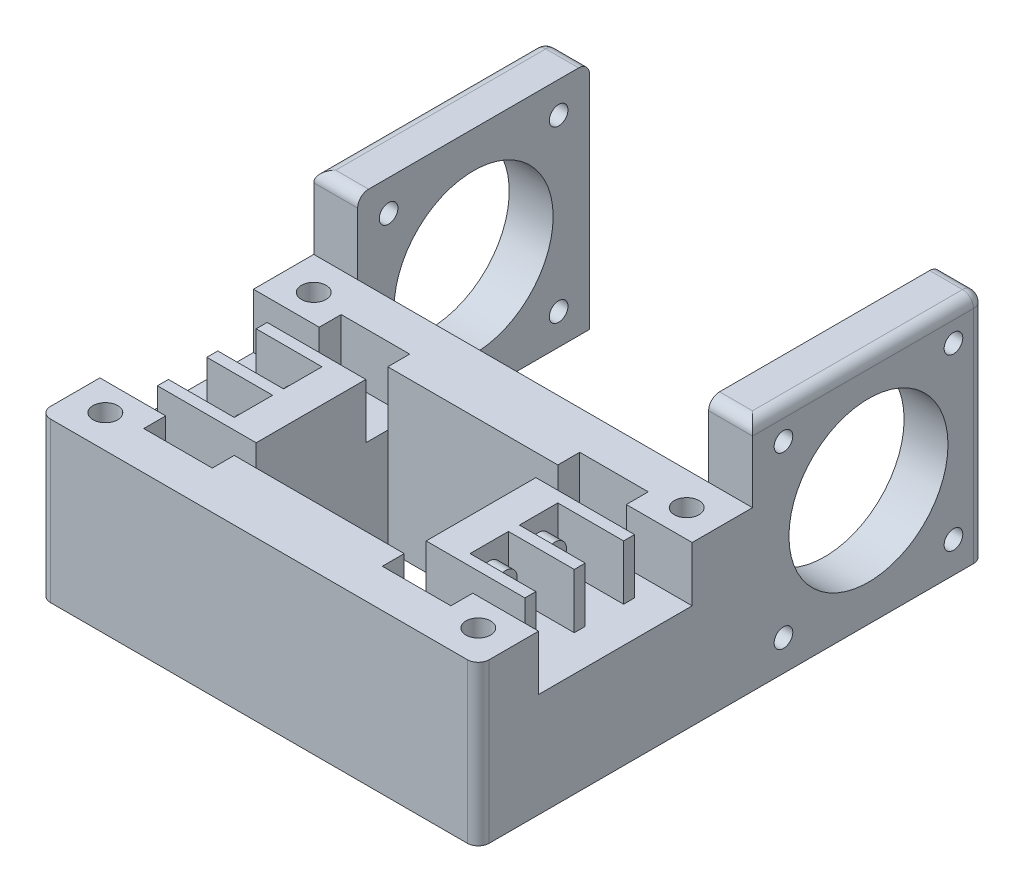
SolidWorks part; units mm, degrees
ref_plane "Front Plane" through (0, 0, 0) normal (0, 0, 1) x (1, 0, 0)
ref_plane "Top Plane" through (0, 0, 0) normal (0, 1, 0) x (1, 0, 0)
ref_plane "Right Plane" through (0, 0, 0) normal (1, 0, 0) x (0, 0, -1)
sketch "Sketch2" plane through (0, 0, 0) normal (0, 1, 0) x (1, 0, 0)
  line L1 (-20, 25) -> (20, 25)
  line L2 (-20, 25) -> (-20, -25)
  line L3 (-20, -25) -> (20, -25)
  line L4 (20, 25) -> (20, -25)
  line L5 (-20, 25) -> (20, -25) construction
  line L6 (-20, -25) -> (20, 25) construction
  line L11 (-20, 25) -> (-20, 67.3)
  line L12 (-20, 67.3) -> (-12, 67.3)
  line L13 (-12, 67.3) -> (-12, 25)
  point P0 (-20, 0)
  dimension "D1" = 40
  dimension "D2" = 50
  dimension "D3" = 20
  dimension "D7" = 8
  dimension "D8" = 42.3
extrude "Boss-Extrude1" add sketch "Sketch2" along normal blind 29 contours L4 L1 L2 L3 region at (0, 0, 0)
sketch "Sketch3" plane through (0, 29, 0) normal (0, 1, 0) x (1, 0, 0)
  line L0 (-20, 14) -> (-8, 14)
  line L1 (-8, 14) -> (-8, 18)
  line L2 (-8, 18) -> (4.5, 18)
  line L3 (4.5, 18) -> (4.5, 14)
  line L4 (4.5, -18) -> (4.5, -14)
  line L5 (4.5, -18) -> (-8, -18)
  line L6 (-8, -18) -> (-8, -14)
  line L7 (-8, -14) -> (-20, -14)
  line L9 (4.5, 10) -> (-13.5, 10)
  line L10 (-13.5, 10) -> (-13.5, 8)
  line L11 (-13.5, 8) -> (-1.5, 8)
  line L12 (-1.5, 8) -> (-1.5, 1)
  line L13 (-1.5, 1) -> (-13.5, 1)
  line L14 (-13.5, 1) -> (-13.5, -1)
  line L15 (-13.5, -1) -> (-1.5, -1)
  line L16 (-1.5, -1) -> (-1.5, -8)
  line L17 (-1.5, -8) -> (-13.5, -8)
  line L18 (-13.5, -8) -> (-13.5, -10)
  line L22 (-13.5, -10) -> (4.5, -10)
  line L28 (-20, 14) -> (-20, -14)
  line L30 (4.5, 14) -> (20, 14)
  line L31 (20, 14) -> (20, -14)
  line L32 (20, -14) -> (4.5, -14)
  line L34 (4.5, 10) -> (4.5, -10)
  line L35 (4.5, 14) -> (4.5, 10)
  line L36 (4.5, -10) -> (4.5, -14)
  line L38 (-20, 25) -> (-20, -25) construction
  line L39 (20, 25) -> (20, -25) construction
  point P18 (-20, 0)
  dimension "D9" = 18
  dimension "D7" = 6.5
  dimension "D2" = 4
  dimension "D3" = 28
  dimension "D4" = 4
  dimension "D5" = 2
  dimension "D6" = 2
  dimension "D8" = 12.5
  dimension "D11" = 12
  dimension "D13" = 4
extrude "Cut-Extrude2" cut sketch "Sketch3" against normal blind 10 contours L36 L22 L18 L17 L16 L15 L14 L13 L12 L11 L10 L9 L3 L2 L1 L0 L7 L6 L5 L4 region at (-14, 29, -13.5645)
sketch "Sketch6" plane through (-1.5, 0, 0) normal (-1, 0, 0) x (0, 0, 1)
  line L0 (-4.5, 24) -> (4.5, 24) construction
  line L4 (-8, 19) -> (-1, 19) construction
  line L5 (1, 19) -> (8, 19) construction
  line L6 (-8, 19) -> (-8, 29) construction
  circle A0 centre (-4.5, 24) radius 2.085
  circle A1 centre (4.5, 24) radius 2.085
  circle A2 centre (-4.5, 24) radius 2.815 construction
  circle A3 centre (4.5, 24) radius 2.815 construction
  point P4 (0, 24)
  point P8 (-4.5, 19)
  point P12 (4.5, 19)
  point P15 (-8, 24)
  dimension "D1" = 4.17
  dimension "D2" = 5.63
extrude "Boss-Extrude2" add sketch "Sketch6" along normal blind 3
extrude "Cut-Extrude3" cut sketch "Sketch3<4>" against normal through all contours L34 L36 L32 L31 L30 region at (12.25, 29, 0)
sketch "Sketch3<4>" plane through (0, 29, 0) normal (0, 1, 0) x (1, 0, 0) same geometry as "Sketch3"
hole_wizard "M4 Clearance Hole2" positions "Sketch11" profile "Sketch12" hole size "M4" standard "ANSI Metric" end condition through all
sketch "Sketch11" plane through (0, 29, 0) normal (0, 1, 0) x (1, 0, 0)
  line L11 (-14, 19) -> (-14, -19) construction
  line L14 (-20, 14) -> (-20, -14) construction
  line L15 (-20, -14) -> (-20, -25) construction
  line L16 (-20, 25) -> (20, 25) construction
  point P4 (-14, -19)
  point P31 (-14, 19)
  point P43 (-20, 0)
  point P44 (-14, 0)
  dimension "D1" = 6
  dimension "D2" = 6
sketch "Sketch12" plane through (-14, 29, 19) normal (1, 0, 0) x (0, 0, 1)
  line L0 (0, 0) -> (0, 29)
  line L1 (0, 29) -> (2.25, 29)
  line L2 (2.25, 29) -> (2.25, 0)
  line L5 (2.25, 0) -> (0, 0)
  line L11 (0, -6.35) -> (0, 107.95) construction
  dimension "Thru Hole Dia." = 4.5
  dimension "Thru Hole Depth" = 29
ref_plane "Plane1" through (20, 0, 0) normal (1, 0, 0) x (0, 0, -1)
extrude "Boss-Extrude3" add sketch "Sketch2<3>" along normal blind 42.3 contours L3 | L13 L12 L11 L1 region at (-16, 0, -46.15)
sketch "Sketch2<3>" plane through (0, 0, 0) normal (0, 1, 0) x (1, 0, 0) same geometry as "Sketch2"
sketch "Sketch15" plane through (-20, 0, 0) normal (-1, 0, 0) x (0, 0, 1)
  line L0 (-67.3, 42.3) -> (-67.3, 0) construction
  line L1 (-25, 42.3) -> (-67.3, 42.3) construction
  circle A0 centre (-46.15, 21.15) radius 14.5
  point P4 (-67.3, 21.15)
  point P7 (-46.15, 42.3)
  dimension "D1" = 29
extrude "Cut-Extrude4" cut sketch "Sketch15" against normal up to next
hole_wizard "M3 Clearance Hole1" positions "Sketch16" profile "Sketch17" hole size "M3" standard "ANSI Metric" end condition up to next
sketch "Sketch16" plane through (-12, 0, 0) normal (-1, 0, 0) x (0, 0, 1)
  line L0 (-30.65, 36.65) -> (-61.65, 36.65) construction
  line L1 (-61.65, 36.65) -> (-61.65, 5.65) construction
  line L2 (-61.65, 5.65) -> (-30.65, 5.65) construction
  line L3 (-30.65, 5.65) -> (-30.65, 36.65) construction
  line L5 (-67.3, 42.3) -> (-67.3, 0) construction
  line L6 (-25, 42.3) -> (-67.3, 42.3) construction
  point P0 (-61.65, 36.65)
  point P2 (-30.65, 36.65)
  point P4 (-61.65, 5.65)
  point P6 (-30.65, 5.65)
  point P16 (-67.3, 21.15)
  point P17 (-61.65, 21.15)
  point P20 (-46.15, 42.3)
  point P21 (-46.15, 36.65)
  dimension "D1" = 31
  dimension "D2" = 31
sketch "Sketch17" plane through (-12, 36.65, -61.65) normal (0, 1, 0) x (0, 0, -1)
  line L0 (0, 0) -> (0, 8)
  line L1 (0, 8) -> (1.7, 8)
  line L2 (1.7, 8) -> (1.7, 0)
  line L5 (1.7, 0) -> (0, 0)
  line L11 (0, -6.35) -> (0, 107.95) construction
  dimension "Thru Hole Dia." = 3.4
  dimension "Thru Hole Depth" = 8
fillet "Fillet1" radius 2 5 edges at (-20, 14.5, 25) (-16, 42.3, -25) (-16, 42.3, -67.3) (-20, 42.3, -46.15) (-20, 21.15, -67.3)
mirror "Mirror1" about plane through (20, 0, 0) normal (1, 0, 0) of "Cut-Extrude4", "M4 Clearance Hole2", "Cut-Extrude3", "Boss-Extrude2", "Cut-Extrude2", "Boss-Extrude1", "Boss-Extrude3", "M3 Clearance Hole1", "Fillet1"
